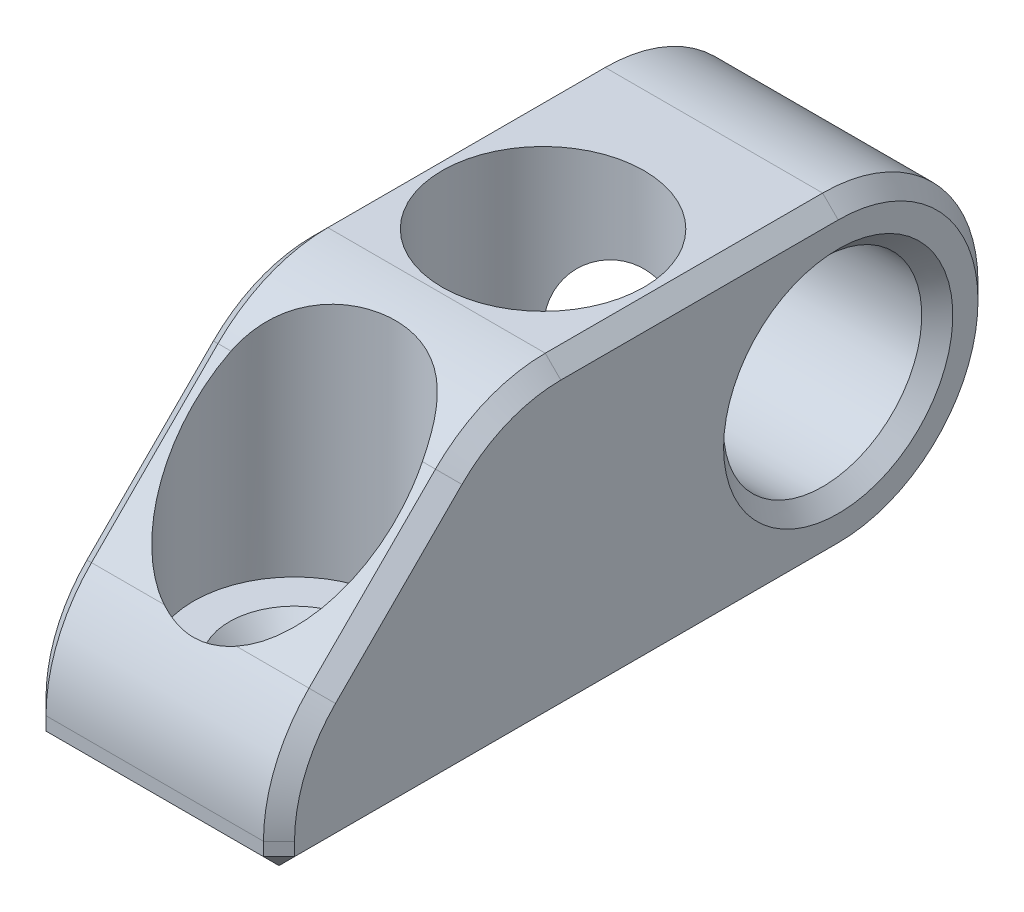
SolidWorks part; units mm, degrees
ref_plane "Front Plane" through (0, 0, 0) normal (0, 0, 1) x (1, 0, 0)
ref_plane "Top Plane" through (0, 0, 0) normal (0, 1, 0) x (1, 0, 0)
ref_plane "Right Plane" through (0, 0, 0) normal (1, 0, 0) x (0, 0, -1)
sketch "Sketch1" plane through (0, 0, 0) normal (0, 1, 0) x (1, 0, 0)
  line L0 (0, 0) -> (0, 1.27) construction
  line L1 (-5.08, -14.605) -> (5.08, -14.605)
  line L2 (-5.08, -14.605) -> (-5.08, 14.605)
  line L3 (-5.08, 14.605) -> (5.08, 14.605)
  line L4 (5.08, -14.605) -> (5.08, 14.605)
  line L5 (-5.08, -14.605) -> (5.08, 14.605) construction
  line L6 (-5.08, 14.605) -> (5.08, -14.605) construction
  line L7 (0, 0) -> (0, -8.89) construction
  circle A0 centre (0, 1.27) radius 2.032
  circle A1 centre (0, -8.89) radius 2.032
  circle A2 centre (0, 1.27) radius 4.1275
  circle A3 centre (0, -8.89) radius 4.1275
  point P0 (0, 0)
  dimension "D3" = 4.064
  dimension "D6" = 8.255
  dimension "D1" = 29.21
  dimension "D2" = 10.16
  dimension "D4" = 8.89
  dimension "D5" = 1.27
extrude "Boss-Extrude1" add sketch "Sketch1" along normal blind 12.7 contours L1 L4 L3 L2 A1 A0 | A1 | A0 | A2 A0 | A3 A1 region at (-4.7707, 0, 0) region at (0, 0, -1.27) region at (0, 0, 8.89) region at (-4.0108, 0, -1.27) region at (-4.0108, 0, 8.89)
sketch "Sketch2" plane through (-5.08, 0, 0) normal (-1, 0, 0) x (0, 0, 1)
  line L0 (-8.255, 0) -> (-8.255, 6.35) construction
  line L1 (14.605, 0) -> (-14.605, 0) construction
  circle A0 centre (-8.255, 6.35) radius 4.05
  dimension "D1" = 8.1
  dimension "D2" = 6.35
  dimension "D3" = 22.86
extrude "Cut-Extrude1" cut sketch "Sketch2" against normal through all contours A0
extrude "Cut-Extrude2" cut sketch "Sketch1<3>" along normal through all contours A0 | A1 region at (0, 0, -1.27) region at (0, 0, 8.89)
sketch "Sketch1<3>" plane through (0, 0, 0) normal (0, 1, 0) x (1, 0, 0) same geometry as "Sketch1"
extrude "Cut-Extrude3" cut sketch "Sketch1<4>" against normal blind 10.16 from surface contours A3 A1 | A2 A0 region at (-4.0108, 0, -1.27) region at (-4.0108, 0, 8.89) starting at face at (0, 12.7, 0.762)
sketch "Sketch1<4>" plane through (0, 0, 0) normal (0, 1, 0) x (1, 0, 0) same geometry as "Sketch1"
chamfer "Chamfer1" distance 8.89 angle 45 1 edges at (0, 12.7, 14.605)
fillet "Fillet1" radius 6.35 3 edges at (0, 3.81, 14.605) (-3.8587, 12.7, 5.715) (3.8587, 12.7, 5.715)
chamfer "Chamfer2" distance 0.635 angle 45 2 edges at (-5.08, 6.35, -4.205) (5.08, 6.35, -4.205)
fillet "Fillet2" radius 6.35 2 edges at (0, 0, -14.605) (0, 12.7, -14.605)
chamfer "Chamfer3" distance 0.635 angle 45 2 edges at (0, 0, 10.922) (0, 0, 0.762)
chamfer "Chamfer4" distance 0.635 angle 45 17 edges at (5.08, 0.5899, 14.605) (-5.08, 0.5899, 14.605) (5.08, 3.6098, 14.1216) (-5.08, 3.6098, 14.1216) (5.08, 8.255, 10.16) (-5.08, 8.255, 10.16) (5.08, 12.2166, 5.5148) (-5.08, 12.2166, 5.5148) (5.08, 12.7, -2.5851) (-5.08, 12.7, -2.5851) (0, 0, 14.605) (-5.08, 0, 3.175) (5.08, 0, 3.175) (-5.08, 10.8401, -12.7451) (5.08, 10.8401, -12.7451) (-5.08, 1.8599, -12.7451) (5.08, 1.8599, -12.7451)
chamfer "Chamfer5" distance 0.635 angle 45 2 edges at (0, 2.54, 0.762) (0, 2.54, 10.922)
